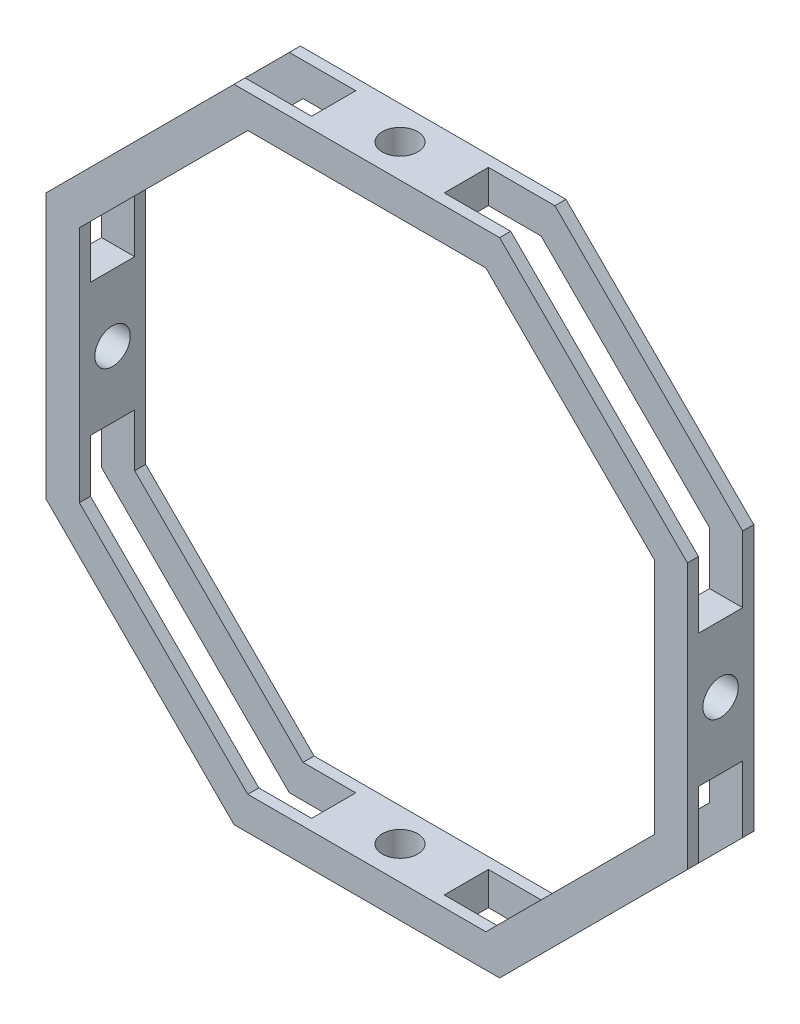
SolidWorks part; units mm, degrees
ref_plane "Plano frontal" through (0, 0, 0) normal (0, 0, 1) x (1, 0, 0)
ref_plane "Plano superior" through (0, 0, 0) normal (0, 1, 0) x (1, 0, 0)
ref_plane "Plano direito" through (0, 0, 0) normal (1, 0, 0) x (0, 0, -1)
sketch "Esboço1" plane through (0, 0, 0) normal (0, 0, 1) x (1, 0, 0)
  line L1 (145, 60.061) -> (60.061, 145)
  line L2 (60.061, 145) -> (-60.061, 145)
  line L3 (-60.061, 145) -> (-145, 60.061)
  line L4 (-145, 60.061) -> (-145, -60.061)
  line L5 (-145, -60.061) -> (-60.061, -145)
  line L6 (-60.061, -145) -> (60.061, -145)
  line L7 (60.061, -145) -> (145, -60.061)
  line L8 (145, -60.061) -> (145, 60.061)
  line L9 (130, 53.8478) -> (53.8478, 130)
  line L10 (53.8478, 130) -> (-53.8478, 130)
  line L11 (-53.8478, 130) -> (-130, 53.8478)
  line L12 (-130, 53.8478) -> (-130, -53.8478)
  line L13 (-130, -53.8478) -> (-53.8478, -130)
  line L14 (-53.8478, -130) -> (53.8478, -130)
  line L15 (53.8478, -130) -> (130, -53.8478)
  line L16 (130, -53.8478) -> (130, 53.8478)
  circle A0 centre (0, 0) radius 145 construction
  circle A1 centre (0, 0) radius 130 construction
extrude "Ressalto-extrusão1" add sketch "Esboço1" along normal blind 30
sketch "Esboço2" plane through (145, 0, 0) normal (1, 0, 0) x (0, 0, -1)
  line L0 (-30, -60.061) -> (-30, 60.061) construction
  line L1 (0, 0) -> (-30, 0)
  line L2 (0, 0) -> (0, 30)
  line L3 (0, 30) -> (-30, 30)
  line L4 (-30, 0) -> (-30, 30)
  line L5 (-30, -60.061) -> (0, -60.061) construction
  line L6 (0, 0) -> (-30, 0)
  line L7 (0, 0) -> (0, -30)
  line L8 (0, -30) -> (-30, -30)
  line L9 (-30, 0) -> (-30, -30)
  line L10 (0, 60.061) -> (-5, 60.061)
  line L11 (0, 60.061) -> (0, 30)
  line L12 (0, 30) -> (-5, 30)
  line L13 (-5, 60.061) -> (-5, 30)
  line L14 (-30, 60.061) -> (-25, 60.061)
  line L15 (-30, 60.061) -> (-30, 30)
  line L16 (-30, 30) -> (-25, 30)
  line L17 (-25, 60.061) -> (-25, 30)
  line L18 (-25, -30) -> (-5, -30)
  line L19 (-25, -30) -> (-25, -60.061)
  line L20 (-25, -60.061) -> (-5, -60.061)
  line L21 (-5, -30) -> (-5, -60.061)
  circle A0 centre (-15, 0) radius 8
  line M2 (0, 60.061) -> (-30, 60.061)
  line M4 (-30, -60.061) -> (0, -60.061)
extrude "Corte-extrusão1" cut sketch "Esboço2" against normal through all both and the other way through all contours L17 L3 L13 M2 | L21 L8 L19 M4 | A0 region at (145, 45.0305, 15) region at (145, -45.0305, 15)
sketch "Esboço3" plane through (102.5305, 102.5305, 0) normal (0.7071, 0.7071, 0) x (0, 0, -1)
  line L0 (-30, 60.061) -> (0, 60.061) construction
  line L1 (-25, -60.061) -> (-5, -60.061)
  line L2 (-25, -60.061) -> (-25, 60.061)
  line L3 (-25, 60.061) -> (-5, 60.061)
  line L4 (-5, -60.061) -> (-5, 60.061)
extrude "Corte-extrusão2" cut sketch "Esboço3" against normal through all both and the other way through all
sketch "Esboço4" plane through (0, 145, 0) normal (0, 1, 0) x (1, 0, 0)
  line L0 (60.061, -30) -> (-60.061, -30) construction
  line L1 (0, 0) -> (30, 0)
  line L2 (0, 0) -> (0, -30)
  line L3 (0, -30) -> (30, -30)
  line L4 (30, 0) -> (30, -30)
  line L5 (-60.061, -30) -> (-60.061, 0) construction
  line L6 (0, 0) -> (-30, 0)
  line L7 (0, 0) -> (0, -30)
  line L8 (0, -30) -> (-30, -30)
  line L9 (-30, 0) -> (-30, -30)
  line L10 (60.061, 0) -> (30, 0)
  line L11 (60.061, 0) -> (60.061, -5)
  line L12 (60.061, -5) -> (30, -5)
  line L13 (30, 0) -> (30, -5)
  line L14 (60.061, -25) -> (30, -25)
  line L15 (60.061, -25) -> (60.061, -30)
  line L16 (60.061, -30) -> (30, -30)
  line L17 (30, -25) -> (30, -30)
  line L18 (-30, -5) -> (-60.061, -5)
  line L19 (-30, -5) -> (-30, -25)
  line L20 (-30, -25) -> (-60.061, -25)
  line L21 (-60.061, -5) -> (-60.061, -25)
  line M2 (-60.061, 0) -> (-60.061, -30)
  line M5 (60.061, -25) -> (60.061, -5)
sketch "Esboço5" plane through (0, 145, 0) normal (0, 1, 0) x (1, 0, 0)
  line L0 (0, 0) -> (0, -30) construction
  circle A0 centre (0, -15) radius 8
extrude "Corte-extrusão3" cut sketch "Esboço5" against normal through all both and the other way through all contours A0
extrude "Corte-extrusão4" cut sketch "Esboço4" against normal through all both and the other way through all contours L14 L12 L4 M5 | L20 L9 L18 M2 region at (45.0305, 145, 15) region at (-45.0305, 145, 15)
sketch "Esboço7" plane through (-102.5305, 102.5305, 0) normal (-0.7071, 0.7071, 0) x (0, 0, 1)
  line L0 (25, 60.061) -> (5, 60.061) construction
  line L1 (5, -60.061) -> (25, -60.061)
  line L2 (5, -60.061) -> (5, 60.061)
  line L3 (5, 60.061) -> (25, 60.061)
  line L4 (25, -60.061) -> (25, 60.061)
  line L5 (25, 60.061) -> (25, 81.3173) construction
extrude "Corte-extrusão5" cut sketch "Esboço7" against normal through all both and the other way through all
